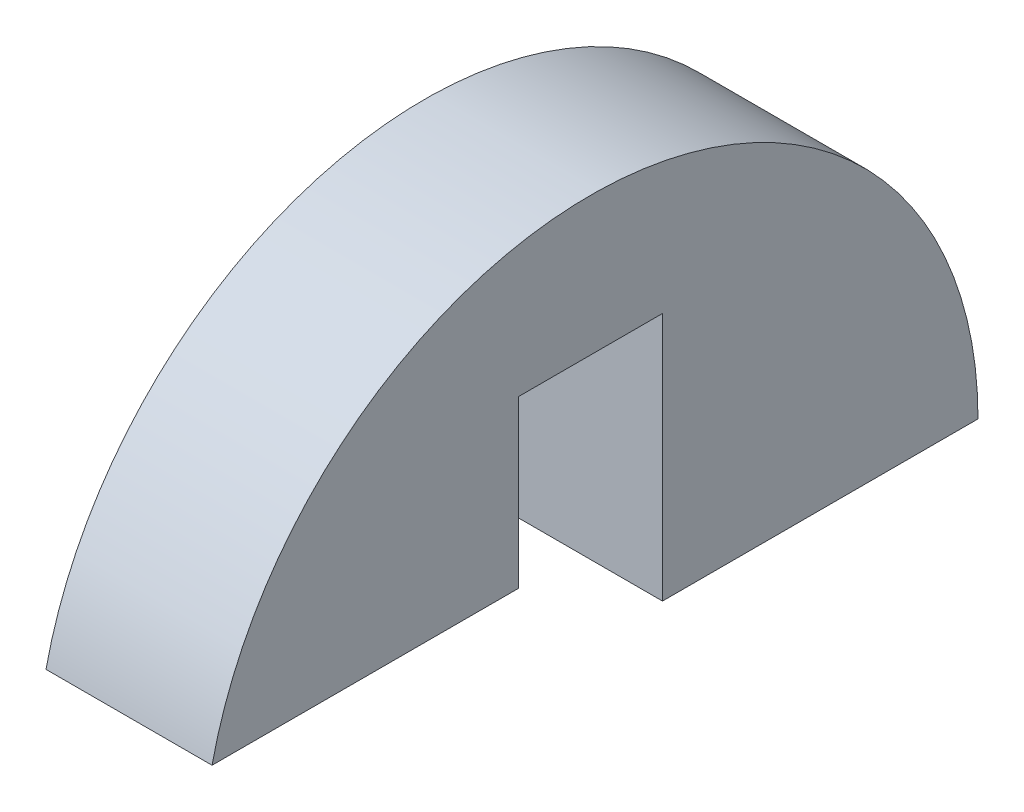
SolidWorks part; units mm, degrees
ref_plane "Front Plane" through (0, 0, 0) normal (0, 0, 1) x (1, 0, 0)
ref_plane "Top Plane" through (0, 0, 0) normal (0, 1, 0) x (1, 0, 0)
ref_plane "Right Plane" through (0, 0, 0) normal (1, 0, 0) x (0, 0, -1)
sketch "Sketch2" plane through (0, 0, 0) normal (0, 1, 0) x (1, 0, 0)
  line L0 (1.5, 1.3) -> (0, 1.3)
  line L1 (0, 1.3) -> (0, 7)
  line L5 (1.5, 6.8374) -> (1.5, 1.3)
  line L6 (1.5, 1.3) -> (4.5, 1.3)
  line L7 (4.5, 1.3) -> (4.5, -1.3)
  line L8 (4.5, -1.3) -> (1.5, -1.3)
  line L9 (1.5, -1.3) -> (1.5, -6.8374)
  line L10 (1.5, 6.8374) -> (1.5, 1.3) construction
  line L11 (1.5, 1.3) -> (4.5, 1.3)
  line L12 (4.5, 1.3) -> (4.5, -1.3)
  line L13 (4.5, -1.3) -> (1.5, -1.3)
  line L14 (1.5, -1.3) -> (1.5, -6.8374)
  arc A0 (1.5, 6.8374) -> (0, 7) centre (0, 0) ccw
  arc A1 (1.5, -6.8374) -> (1.5, 6.8374) centre (0, 0) ccw
  arc A2 (1.5, -6.8374) -> (1.5, 6.8374) centre (0, 0) ccw
  dimension "D1" = 0
extrude "Boss-Extrude1" add sketch "Sketch2" along normal blind 1.5 and the other way blind 1.5
ref_axis "Axis1" through (0, 0, -7.6907) along (0, 0, 1)
move or copy body "Body-Move/Copy1" bodies to move or copy 101 copy no rotation origin (0, 0, 0) rotation axis (0, 0, 1) rotation angle 90
